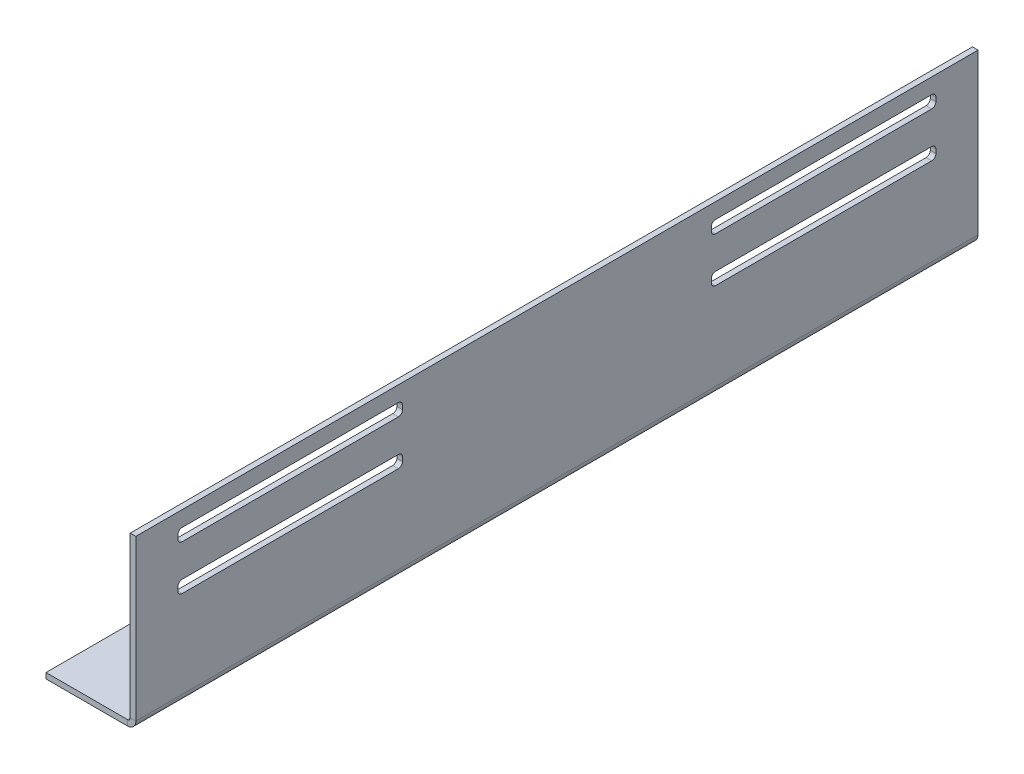
SolidWorks part; units mm, degrees
note: The reader was unsure of these and kept them because the rebuilt part matched: flange length of "Edge-Flange1".
ref_plane "Front Plane" through (0, 0, 0) normal (0, 0, 1) x (1, 0, 0)
ref_plane "Top Plane" through (0, 0, 0) normal (0, 1, 0) x (1, 0, 0)
ref_plane "Right Plane" through (0, 0, 0) normal (1, 0, 0) x (0, 0, -1)
sketch "Sketch1" plane through (0, -95.4759, 0) normal (0, 1, 0) x (1, 0, 0)
  line L1 (-46.8865, -105.5283) -> (-16.8865, -105.5283)
  line L2 (-46.8865, -105.5283) -> (-46.8865, -405.5283)
  line L3 (-46.8865, -405.5283) -> (-16.8865, -405.5283)
  line L4 (-16.8865, -105.5283) -> (-16.8865, -405.5283)
  dimension "D1" = 300
  dimension "D2" = 30
sheet metal parameters "Sheet-Metal1" thickness 2 parameters "D1"=1
base flange "Base-Flange1" sketch "Sketch1" thickness 2 reverse thickness direction yes parameters "D1"=1
edge flange "Edge-Flange1" sketch "Sketch7" flange angle 90 flange length 60 flange position material outside bend radius 1 thickness 2 relief rectangular parameters "D6"=10
sketch "Sketch7" plane through (-16.8865, -93.4759, 0) normal (1, 0, 0) x (0, 0, -1)
  line L0 (-405.5283, 0) -> (-105.5283, 0) construction
  line L1 (-405.5283, 0) -> (-105.5283, 0)
  line L2 (-405.5283, 0) -> (-405.5283, 58)
  line L3 (-405.5283, 58) -> (-105.5283, 58)
  line L4 (-105.5283, 58) -> (-105.5283, 0)
bend "EdgeBend1" bend radius 1 bend angle 90 parameters "D5"=1
sketch "Sketch8" plane through (-14.8865, 0, 0) normal (1, 0, 0) x (0, 0, -1)
  line L1 (-120.5283, -40.9759) -> (-200.5283, -40.9759)
  line L2 (-120.5283, -40.9759) -> (-120.5283, -45.3759)
  line L3 (-120.5283, -45.3759) -> (-200.5283, -45.3759)
  line L4 (-200.5283, -40.9759) -> (-200.5283, -45.3759)
  line L5 (-105.5283, -92.4759) -> (-105.5283, -35.4759) construction
  line L6 (-105.5283, -35.4759) -> (-405.5283, -35.4759) construction
  line L7 (-405.5283, -35.4759) -> (-405.5283, -92.4759) construction
  line L8 (-120.5283, -56.9759) -> (-200.5283, -56.9759)
  line L9 (-120.5283, -56.9759) -> (-120.5283, -61.3759)
  line L10 (-120.5283, -61.3759) -> (-200.5283, -61.3759)
  line L11 (-200.5283, -56.9759) -> (-200.5283, -61.3759)
  line L12 (-390.5283, -40.9759) -> (-310.5283, -40.9759)
  line L13 (-390.5283, -40.9759) -> (-390.5283, -45.3759)
  line L14 (-390.5283, -45.3759) -> (-310.5283, -45.3759)
  line L15 (-310.5283, -40.9759) -> (-310.5283, -45.3759)
  line L16 (-390.5283, -56.9759) -> (-310.5283, -56.9759)
  line L17 (-390.5283, -56.9759) -> (-390.5283, -61.3759)
  line L18 (-390.5283, -61.3759) -> (-310.5283, -61.3759)
  line L19 (-310.5283, -56.9759) -> (-310.5283, -61.3759)
  dimension "D1" = 80
  dimension "D2" = 15
  dimension "D3" = 4.4
  dimension "D4" = 5.5
  dimension "D5" = 80
  dimension "D6" = 4.4
  dimension "D7" = 11.6
  dimension "D8" = 15
  dimension "D9" = 80
  dimension "D10" = 15
  dimension "D11" = 15
  dimension "D12" = 80
  dimension "D13" = 4.4
  dimension "D14" = 4.4
  dimension "D15" = 11.6
  dimension "D16" = 5.5
extrude "Cut-Extrude1" cut sketch "Sketch8" against normal up to next normal cut yes
fillet "Fillet1" radius 1.5 16 edges at (-15.8865, -56.9759, 120.5283) (-15.8865, -61.3759, 120.5283) (-15.8865, -45.3759, 120.5283) (-15.8865, -40.9759, 120.5283) (-15.8865, -61.3759, 200.5283) (-15.8865, -56.9759, 200.5283) (-15.8865, -40.9759, 200.5283) (-15.8865, -45.3759, 200.5283) (-15.8865, -40.9759, 310.5283) (-15.8865, -45.3759, 310.5283) (-15.8865, -56.9759, 310.5283) (-15.8865, -61.3759, 310.5283) (-15.8865, -61.3759, 390.5283) (-15.8865, -56.9759, 390.5283) (-15.8865, -45.3759, 390.5283) (-15.8865, -40.9759, 390.5283)
flat pattern "Flat-Pattern1" [suppressed]
sketch "Bend-Lines1" plane through (0, 0, 0) normal (0, 1, 0) x (-1, 0, 0)
sketch3d "Bounding-Box1" [suppressed]
  line L0 (0, -280, 0) -> (0, 0, 0) construction
  line L1 (40, -280, 0) -> (40, 0, 0) construction
  line L2 (0, -280, 0) -> (40, -280, 0) construction
  line L3 (0, 0, 0) -> (40, 0, 0) construction
bend of the flat pattern "Flatten-<EdgeBend1>1"
